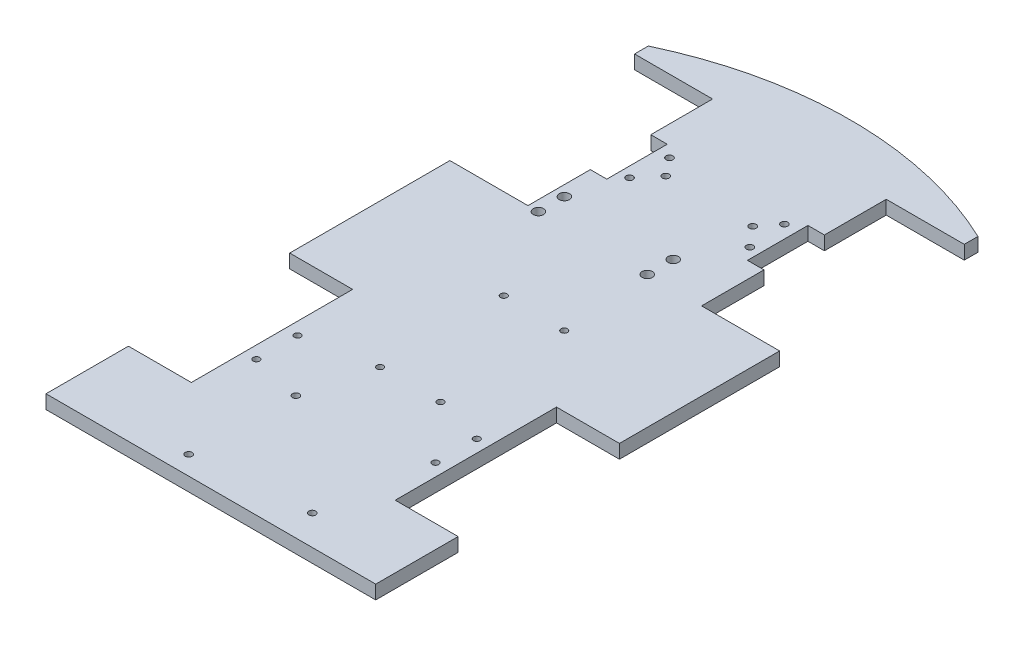
SolidWorks part; units mm, degrees
material "Oak"
ref_plane "Front Plane" through (0, 0, 0) normal (0, 0, 1) x (1, 0, 0)
ref_plane "Top Plane" through (0, 0, 0) normal (0, 1, 0) x (1, 0, 0)
ref_plane "Right Plane" through (0, 0, 0) normal (1, 0, 0) x (0, 0, -1)
sketch "Sketch1" plane through (0, 0, 0) normal (0, 1, 0) x (1, 0, 0)
  line L0 (50.292, 32.512) -> (76.2, 32.512) construction
  line L1 (0, 0) -> (0, -280.955) construction
  line L2 (0, 66.1738) -> (0, -229.362)
  line L3 (76.2, -229.362) -> (0, -229.362)
  line L7 (50.292, 32.512) -> (50.292, -32.512) construction
  line L8 (50.292, -32.512) -> (76.2, -32.512) construction
  line L9 (76.2, 32.512) -> (76.2, -32.512) construction
  line L10 (50.292, 32.512) -> (76.2, -32.512) construction
  line L11 (50.292, -32.512) -> (76.2, 32.512) construction
  line L18 (50.292, -119.888) -> (76.2, -119.888) construction
  line L19 (50.292, -119.888) -> (50.292, -184.912) construction
  line L20 (50.292, -184.912) -> (76.2, -184.912) construction
  line L21 (76.2, -119.888) -> (76.2, -184.912) construction
  line L22 (50.292, -119.888) -> (76.2, -184.912) construction
  line L23 (50.292, -184.912) -> (76.2, -119.888) construction
  line L25 (-76.2, 0) -> (76.2, 0) construction
  line L27 (-76.2, -152.4) -> (76.2, -152.4) construction
  line L28 (76.2, 0) -> (76.2, -152.4) construction
  line L33 (40.132, -42.672) -> (76.2, -42.672)
  line L34 (40.132, 42.672) -> (40.132, 14.097)
  line L35 (40.132, 42.672) -> (76.2, 42.672)
  line L36 (47.117, -191.262) -> (76.2, -191.262)
  line L37 (47.117, -116.713) -> (47.117, -191.262)
  line L38 (47.117, -116.713) -> (76.2, -116.713)
  line L43 (76.2, -42.672) -> (76.2, -116.713)
  line L45 (76.2, 42.672) -> (76.2, 49.022)
  line L47 (76.2, -191.262) -> (76.2, -229.362)
  line L55 (32.512, -13.843) -> (40.132, -13.843)
  line L56 (32.512, 14.097) -> (32.512, -13.843)
  line L57 (32.512, 14.097) -> (40.132, 14.097)
  line L58 (40.132, -13.843) -> (40.132, -42.672)
  arc A0 (0, 66.1738) -> (76.2, 49.022) centre (0, -111.6688) cw
  point P9 (63.246, 0)
  point P19 (63.246, -152.4)
  dimension "D7" = 3.175
  dimension "D8" = 6.35
  dimension "D12" = 7.62
  dimension "D16" = 6.35
  dimension "D1" = 152.4
  dimension "D2" = 152.4
  dimension "D3" = 126.492
  dimension "D4" = 25.908
  dimension "D6" = 3.175
  dimension "D9" = 10.16
  dimension "D10" = 10.16
  dimension "D5" = 65.024
  dimension "D11" = 10.16
  dimension "D13" = 27.94
  dimension "D14" = 28.575
  dimension "D15" = 38.1
extrude "Chassis" add sketch "Sketch1" along normal blind 6.35 contours L47 L36 L37 L38 L43 L33 L34 L55 L56 L57 L35 L45 region at (30.845, 0, 91.965)
mirror "Mirror1" about plane through (0, 6.35, 0) normal (1, 0, 0) of "Chassis"
sketch "Sketch2" plane through (0, 0, 0) normal (0, 1, 0) x (1, 0, 0)
  circle A0 centre (-26.5557, 9.17) radius 1.5875 construction
  circle A1 centre (-17.7031, -172.3599) radius 1.5875
  circle A2 centre (-17.7031, -172.3599) radius 1.5875
  circle A3 centre (-18.9731, -220.6199) radius 1.5875
  circle A4 centre (-18.9731, -220.6199) radius 1.5875
  circle A5 centre (33.0969, -215.5399) radius 1.5875
  circle A6 centre (33.0969, -215.5399) radius 1.5875
  circle A7 centre (-20.1056, 0.9994) radius 1.5875 construction
  circle A8 centre (-27.7865, -8.0406) radius 1.5875 construction
  circle A9 centre (26.5557, 9.17) radius 1.5875 construction
  circle A10 centre (20.1056, 0.9994) radius 1.5875 construction
  circle A11 centre (27.7865, -8.0406) radius 1.5875 construction
  circle A12 centre (15, -30.6528) radius 2.3812 construction
  circle A13 centre (15, -42.6528) radius 2.3813 construction
  circle A14 centre (-35.3, -30.6528) radius 2.3813 construction
  circle A15 centre (-35.3, -42.6528) radius 2.3813 construction
  circle A16 centre (18.288, -84.328) radius 1.5 construction
  circle A17 centre (-9.652, -84.328) radius 1.5 construction
  circle A18 centre (18.288, -141.478) radius 1.5 construction
  circle A19 centre (-9.652, -141.478) radius 1.5 construction
  circle A20 centre (-41.402, -147.875) radius 1.5 construction
  circle A21 centre (-41.402, -166.925) radius 1.5 construction
  circle A22 centre (41.402, -147.875) radius 1.5 construction
  circle A23 centre (41.402, -166.925) radius 1.5 construction
  circle A24 centre (-26.5557, 9.17) radius 1.5875
  circle A25 centre (-20.1056, 0.9994) radius 1.5875
  circle A26 centre (-27.7865, -8.0406) radius 1.5875
  circle A27 centre (26.5557, 9.17) radius 1.5875
  circle A28 centre (20.1056, 0.9994) radius 1.5875
  circle A29 centre (27.7865, -8.0406) radius 1.5875
  circle A30 centre (15, -30.6528) radius 2.3812
  circle A31 centre (15, -42.6528) radius 2.3813
  circle A32 centre (-35.3, -30.6528) radius 2.3813
  circle A33 centre (-35.3, -42.6528) radius 2.3812
  circle A34 centre (18.288, -84.328) radius 1.5
  circle A35 centre (-9.652, -84.328) radius 1.5
  circle A36 centre (18.288, -141.478) radius 1.5
  circle A37 centre (-9.652, -141.478) radius 1.5
  circle A38 centre (-41.402, -147.875) radius 1.5
  circle A39 centre (-41.402, -166.925) radius 1.5
  circle A40 centre (41.402, -147.875) radius 1.5
  circle A41 centre (41.402, -166.925) radius 1.5
  dimension "D1" = 0
  dimension "D2" = 0
  dimension "D3" = 0
extrude "Cut-Extrude1" cut sketch "Sketch2" along normal blind 17.78
